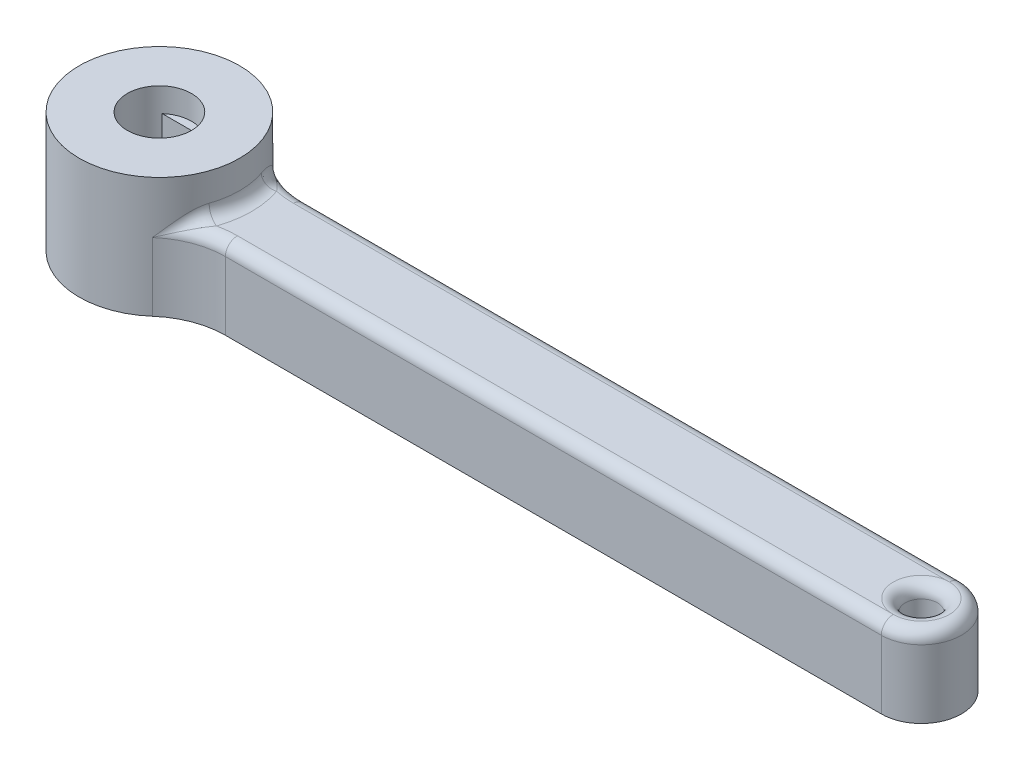
SolidWorks part; units mm, degrees
ref_plane "Front Plane" through (0, 0, 0) normal (0, 0, 1) x (1, 0, 0)
ref_plane "Top Plane" through (0, 0, 0) normal (0, 1, 0) x (1, 0, 0)
ref_plane "Right Plane" through (0, 0, 0) normal (1, 0, 0) x (0, 0, -1)
sketch "Sketch1" plane through (0, 0, 0) normal (0, 1, 0) x (1, 0, 0)
  line L0 (0, 3) -> (-2.6458, 3)
  line L1 (0, 3) -> (2.6458, 3)
  line L4 (13.2288, -5) -> (95, -5)
  line L5 (13.2288, 5) -> (95, 5)
  arc A0 (6.6144, 7.5) -> (6.6144, -7.5) centre (0, 0) ccw
  arc A1 (-2.6458, 3) -> (2.6458, 3) centre (0, 0) ccw
  arc A3 (95, -5) -> (95, 5) centre (95, 0) ccw
  arc A4 (13.2288, 5) -> (6.6144, 7.5) centre (13.2288, 15) cw
  arc A5 (13.2288, -5) -> (6.6144, -7.5) centre (13.2288, -15) ccw
  circle A6 centre (95, 0) radius 2
  dimension "D1" = 10
  dimension "D2" = 10
extrude "Boss-Extrude1" add sketch "Sketch1" along normal blind 10
sketch "Sketch2" plane through (0, 10, 0) normal (0, 1, 0) x (1, 0, 0)
  line L0 (-2.6458, 3) -> (2.6458, 3)
  circle A0 centre (0, 0) radius 10
  arc A1 (-2.6458, 3) -> (2.6458, 3) centre (0, 0) ccw
extrude "Boss-Extrude2" add sketch "Sketch2" along normal blind 5
sketch "Sketch3" plane through (0, 15, 0) normal (0, 1, 0) x (1, 0, 0)
  circle A0 centre (0, 0) radius 4
extrude "Cut-Extrude1" cut sketch "Sketch3" against normal blind 3
fillet "Fillet1" radius 1.5 7 edges at (9.6932, 10, -5.6459) (54.1144, 10, -5) (100, 10, 0) (54.1144, 10, 5) (9.6932, 10, 5.6459) (10, 10, 0) (95, 10, 2)
